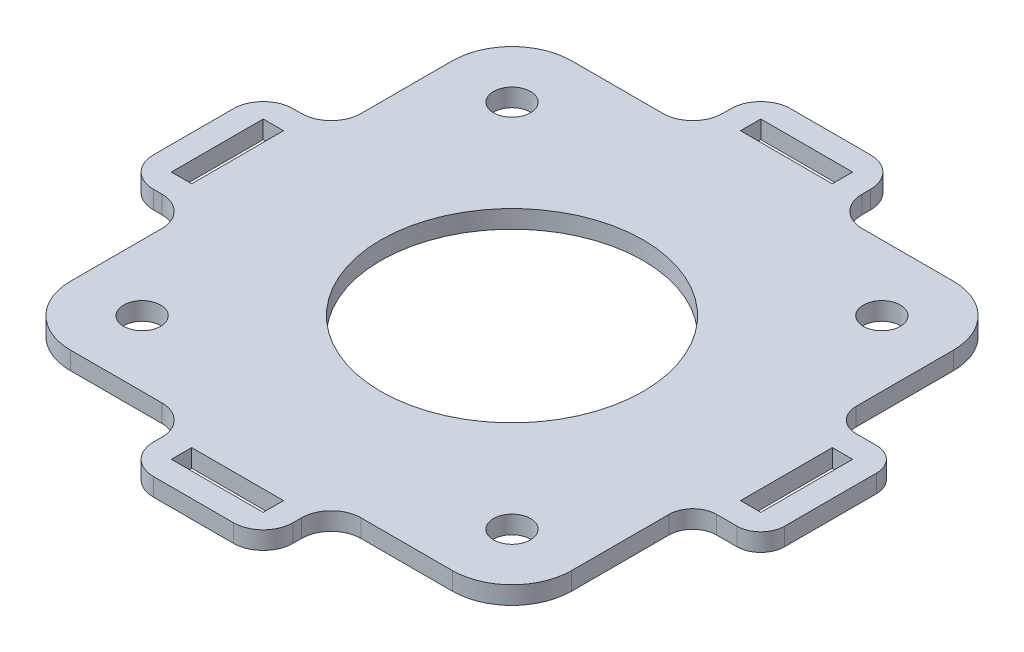
SolidWorks part; units mm, degrees
material "AISI 304"
ref_plane "Front Plane" through (0, 0, 0) normal (0, 0, 1) x (1, 0, 0)
ref_plane "Top Plane" through (0, 0, 0) normal (0, 1, 0) x (1, 0, 0)
ref_plane "Right Plane" through (0, 0, 0) normal (1, 0, 0) x (0, 0, -1)
sketch "Sketch1" plane through (0, 0, 0) normal (0, 1, 0) x (1, 0, 0)
  line L0 (0, 0) -> (0, 33.6449) construction
  line L5 (0, 0) -> (35.5051, 0) construction
  line L6 (3.85, -23) -> (3.85, -24.7)
  line L40 (23, 3.85) -> (24.7, 3.85)
  line L41 (23, 3.85) -> (23, -3.85)
  line L62 (23, -3.85) -> (24.7, -3.85)
  line L63 (24.7, 3.85) -> (24.7, -3.85)
  line L64 (23, 3.85) -> (24.7, -3.85) construction
  line L65 (23, -3.85) -> (24.7, 3.85) construction
  line L66 (21, 5.85) -> (26.7, 5.85)
  line L68 (21, -5.85) -> (26.7, -5.85)
  line L69 (26.7, 5.85) -> (26.7, -5.85)
  line L70 (21, 21) -> (5.85, 21)
  line L71 (21, 21) -> (21, 5.85)
  line L72 (21, -21) -> (5.85, -21)
  line L73 (-21, 21) -> (-21, 5.85)
  line L74 (21, 21) -> (-21, -21) construction
  line L75 (21, -21) -> (-21, 21) construction
  line L76 (3.85, -23) -> (-3.85, -23)
  line L77 (-3.85, -23) -> (-3.85, -24.7)
  line L78 (3.85, -24.7) -> (-3.85, -24.7)
  line L79 (5.85, -26.7) -> (-5.85, -26.7)
  line L80 (3.85, -23) -> (-3.85, -24.7) construction
  line L81 (-3.85, -23) -> (3.85, -24.7) construction
  line L82 (5.85, -21) -> (5.85, -26.7)
  line L83 (-5.85, -21) -> (-5.85, -26.7)
  line L84 (-23, -3.85) -> (-24.7, -3.85)
  line L85 (-23, -3.85) -> (-23, 3.85)
  line L86 (-23, 3.85) -> (-24.7, 3.85)
  line L87 (-24.7, -3.85) -> (-24.7, 3.85)
  line L88 (-26.7, -5.85) -> (-26.7, 5.85)
  line L89 (-23, -3.85) -> (-24.7, 3.85) construction
  line L90 (-23, 3.85) -> (-24.7, -3.85) construction
  line L91 (-21, -5.85) -> (-26.7, -5.85)
  line L92 (-21, 5.85) -> (-26.7, 5.85)
  line L93 (-3.85, 23) -> (-3.85, 24.7)
  line L94 (-3.85, 23) -> (3.85, 23)
  line L95 (3.85, 23) -> (3.85, 24.7)
  line L96 (-3.85, 24.7) -> (3.85, 24.7)
  line L97 (-5.85, 26.7) -> (5.85, 26.7)
  line L98 (-3.85, 23) -> (3.85, 24.7) construction
  line L99 (3.85, 23) -> (-3.85, 24.7) construction
  line L100 (-5.85, 21) -> (-5.85, 26.7)
  line L101 (5.85, 21) -> (5.85, 26.7)
  line L102 (-5.85, -21) -> (-21, -21)
  line L103 (-5.85, 21) -> (-21, 21)
  line L104 (-21, -5.85) -> (-21, -21)
  line L105 (21, -5.85) -> (21, -21)
  circle A1 centre (-15.5, 15.5) radius 1.55
  circle A2 centre (15.5, 15.5) radius 1.55
  circle A3 centre (15.5, -15.5) radius 1.55
  circle A4 centre (-15.5, -15.5) radius 1.55
  circle A5 centre (0, 0) radius 11
  point P0 (0, 0)
  point P3 (23.85, 0)
  point P22 (0, 0)
  point P25 (0, -23.85)
  point P37 (-23.85, 0)
  point P46 (0, 23.85)
  point P55 (0, 0)
  point P66 (0, 0)
  point P84 (0, 0)
  dimension "D1" = 42
  dimension "D2" = 3.1
  dimension "D8" = 2
  dimension "D15" = 22
  dimension "D9" = 15.5
  dimension "D3" = 2
  dimension "D4" = 2
  dimension "D5" = 42
  dimension "D10" = 2
  dimension "D11" = 1.7
  dimension "D12" = 7.7
  dimension "D13" = 4
  dimension "D14" = 15.5
  dimension "D6" = 2
  dimension "D7" = 2
extrude "Boss-Extrude1" add sketch "Sketch1" along normal blind 1.5
fillet "Fillet2" radius 5 4 edges at (21, 0.75, 21) (-21, 0.75, 21) (-21, 0.75, -21) (21, 0.75, -21)
fillet "Fillet3" radius 2 4 edges at (26.7, 0.75, -5.85) (21, 0.75, -5.85) (21, 0.75, 5.85) (26.7, 0.75, 5.85)
fillet "Fillet1" radius 2.5 12 edges at (-21, 0.75, -5.85) (-26.7, 0.75, -5.85) (-21, 0.75, 5.85) (-26.7, 0.75, 5.85) (-5.85, 0.75, 26.7) (-5.85, 0.75, 21) (5.85, 0.75, 26.7) (5.85, 0.75, 21) (5.85, 0.75, -21) (5.85, 0.75, -26.7) (-5.85, 0.75, -26.7) (-5.85, 0.75, -21)
